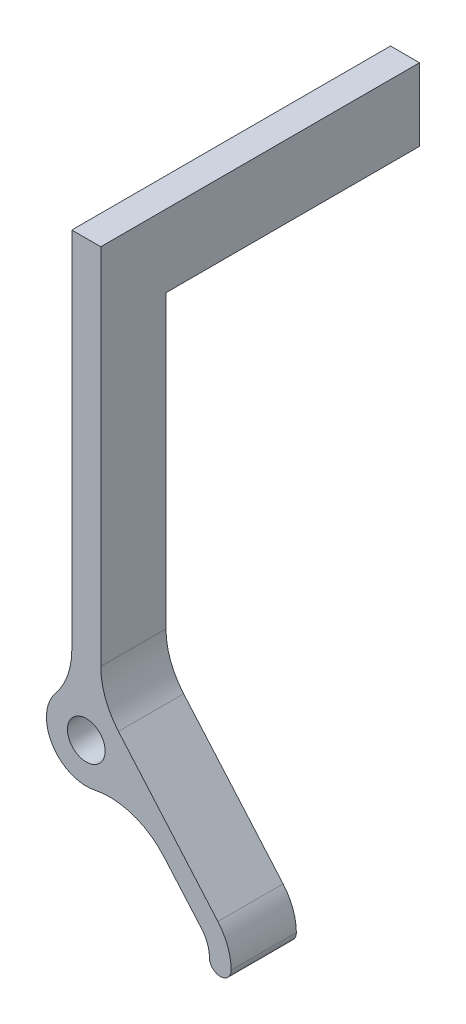
SolidWorks part; units mm, degrees
material "ABS"
ref_plane "Front Plane" through (0, 0, 0) normal (0, 0, 1) x (1, 0, 0)
ref_plane "Top Plane" through (0, 0, 0) normal (0, 1, 0) x (1, 0, 0)
ref_plane "Right Plane" through (0, 0, 0) normal (1, 0, 0) x (0, 0, -1)
sketch "Sketch1" plane through (0, 0, 0) normal (0, 0, 1) x (1, 0, 0)
  line L0 (4.1588, 3.5992) -> (18.1711, -12.592)
  line L2 (15.9027, -14.5552) -> (5.0962, -2.0684)
  line L3 (2, 5.1235) -> (2, 60)
  line L4 (2, 60) -> (-2, 60)
  line L5 (-2, 60) -> (-2, 5.1235)
  circle A0 centre (0, 0) radius 2.6
  arc A1 (4.1588, 3.5992) -> (2, 5.1235) centre (0, 0) ccw
  arc A2 (-2, 5.1235) -> (5.0962, -2.0684) centre (0, 0) ccw
  arc A4 (15.9027, -14.5552) -> (17, -17.5) centre (12.5, -17.5) cw
  arc A5 (17, -17.5) -> (20, -17.5) centre (18.5, -17.5) ccw
  arc A6 (18.1711, -12.592) -> (20, -17.5) centre (12.5, -17.5) cw
  circle A7 centre (12.5, -17.5) radius 4.5 construction
  point P10 (0, 60)
  dimension "D1" = 5.2
  dimension "D2" = 5.5
  dimension "D8" = 17.5
  dimension "D5" = 1.5
  dimension "D9" = 9
  dimension "D3" = 3
  dimension "D4" = 12.5
  dimension "D6" = 4
  dimension "D7" = 60
extrude "Boss-Extrude1" add sketch "Sketch1" along normal blind 9
fillet "Fillet1" radius 10 3 edges at (5.0962, -2.0684, 4.5) (-2, 5.1235, 4.5) (2, 5.1235, 4.5)
sketch "Sketch2" plane through (0, 0, 0) normal (0, 0, -1) x (-1, 0, 0)
  line L0 (-2, 9.82) -> (-2, 60) construction
  line L1 (2, 60) -> (-2, 60)
  line L2 (2, 60) -> (2, 50)
  line L3 (2, 50) -> (-2, 50)
  line L4 (-2, 60) -> (-2, 50)
  dimension "D1" = 10
extrude "Boss-Extrude2" add sketch "Sketch2" along normal blind 35
